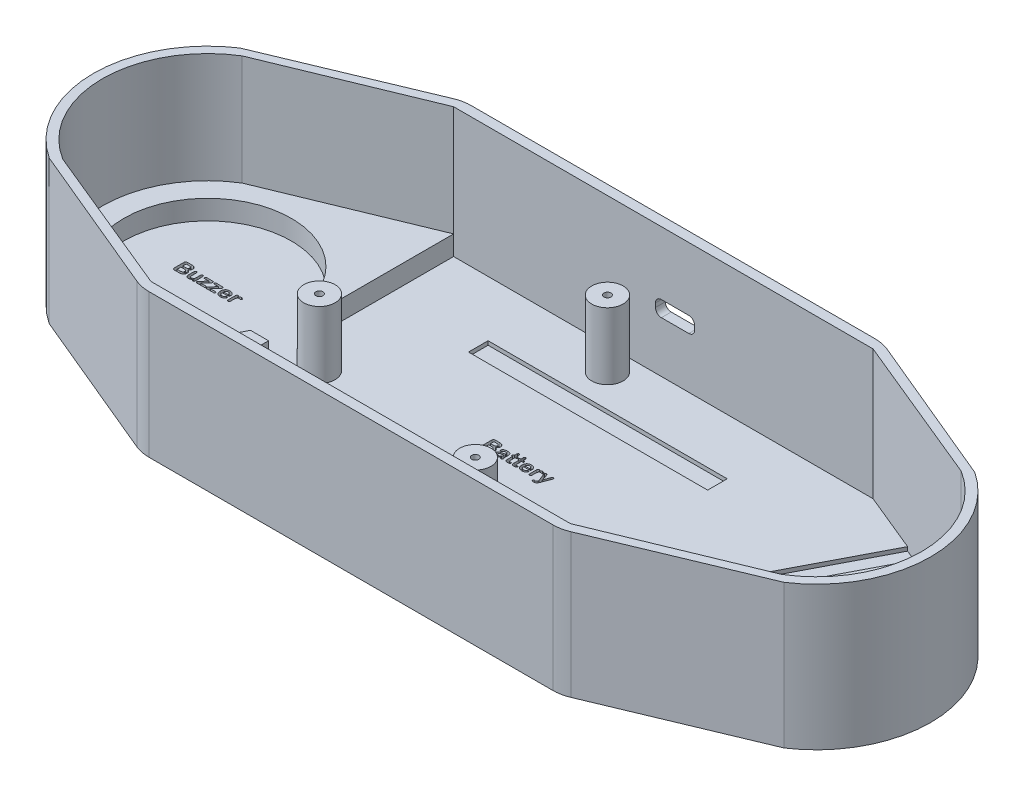
SolidWorks part; units mm, degrees
ref_plane "Front Plane" through (0, 0, 0) normal (0, 0, 1) x (1, 0, 0)
ref_plane "Top Plane" through (0, 0, 0) normal (0, 1, 0) x (1, 0, 0)
ref_plane "Right Plane" through (0, 0, 0) normal (1, 0, 0) x (0, 0, -1)
sketch "Sketch2" plane through (0, 0, 0) normal (0, 1, 0) x (1, 0, 0)
  line L0 (0, 0) -> (102, 0) construction
  line L1 (0, 0) -> (0, -77.2) construction
  line L2 (102, 0) -> (102, -77.2) construction
  line L3 (0, -77.2) -> (102, -77.2) construction
  line L4 (51, 0) -> (51, -77.2) construction
  line L5 (0, -38.6) -> (102, -38.6) construction
  line L6 (-2.5, 2.5) -> (104.5, 2.5)
  line L7 (-2.5, -79.7) -> (104.5, -79.7)
  line L8 (104.5, 2.5) -> (144.7372, -14.2911)
  line L9 (104.5, -79.7) -> (144.7372, -62.9089)
  line L10 (102, -38.6) -> (155.3, -38.6) construction
  line L11 (-2.5, -79.7) -> (-42.7372, -62.9089)
  line L12 (-2.5, 2.5) -> (-42.7372, -14.2911)
  line L13 (0, 0) -> (102, 0)
  line L14 (102, 0) -> (104.5, 0)
  line L15 (104.5, 0) -> (142.7026, -15.7437)
  line L16 (104.5, -77.2) -> (142.7026, -61.4563)
  line L17 (102, -77.2) -> (104.5, -77.2)
  line L18 (-2.5, -77.2) -> (-40.7026, -61.4563)
  line L19 (0, -77.2) -> (-2.5, -77.2)
  line L20 (-2.5, 0) -> (-40.7026, -15.7437)
  line L21 (0, 0) -> (-2.5, 0)
  line L22 (0, -77.2) -> (102, -77.2)
  line L23 (0, -76.7) -> (102, -76.7) construction
  line L24 (-2.5, -38.6) -> (-53.4807, -38.6) construction
  line L25 (-2.5, 0) -> (-2.5, -77.2) construction
  line L26 (104.5, 0) -> (104.5, -77.2) construction
  line L27 (0.5, 0) -> (0.5, -77.2) construction
  arc A0 (144.7372, -14.2911) -> (144.7372, -62.9089) centre (128.65, -38.6) cw
  arc A1 (-42.7372, -14.2911) -> (-42.7372, -62.9089) centre (-26.65, -38.6) ccw
  arc A2 (142.7026, -15.7437) -> (142.7026, -61.4563) centre (128.65, -38.6) cw
  arc A3 (-40.7026, -15.7437) -> (-40.7026, -61.4563) centre (-26.65, -38.6) ccw
  circle A4 centre (5.55, -71.7) radius 1.1
  circle A5 centre (5.6, -42.325) radius 1.1
  circle A6 centre (61.615, -58.575) radius 1.1
  circle A7 centre (42.614, -5.87) radius 1.1
  point P16 (157.8, -38.6)
  dimension "D3" = 2.5
  dimension "D10" = 2.5
  dimension "D11" = 5.05
  dimension "D12" = 5
  dimension "D13" = 34.375
  dimension "D15" = 18.125
  dimension "D17" = 42.114
  dimension "D1" = 77.2
  dimension "D2" = 102
  dimension "D4" = 2.5
  dimension "D5" = 2.5
  dimension "D6" = 2.5
  dimension "D7" = 0.5
  dimension "D8" = 2.5
  dimension "D9" = 53.3
  dimension "D14" = 5.1
  dimension "D16" = 61.115
  dimension "D18" = 70.83
  dimension "D19" = 0.5
extrude "MainExtrude" add sketch "Sketch2" along normal blind 33.1 contours A1 L11 L7 L9 A0 L8 L6 L12
extrude "MainCut" cut sketch "Sketch2<5>" along normal blind 50.8 contours L20 A3 L18 L19 L22 L17 L16 A2 L15 L14 L13 L21
sketch "Sketch2<5>" plane through (0, 0, 0) normal (0, 1, 0) x (1, 0, 0) same geometry as "Sketch2"
extrude "BassExtrude" add sketch "Sketch2<6>" against normal blind 3.5 contours L12 A1 L11 L7 L9 A0 L8 L6
sketch "Sketch2<6>" plane through (0, 0, 0) normal (0, 1, 0) x (1, 0, 0) same geometry as "Sketch2"
fillet "Fillet1" radius 10 4 edges at (104.5, 14.8, -2.5) (-2.5, 14.8, -2.5) (104.5, 14.8, 79.7) (-2.5, 14.8, 79.7)
sketch "Sketch6" plane through (0, 0, 0) normal (0, 1, 0) x (1, 0, 0)
  line L1 (-2.5, 0) -> (-2.5, -30)
  line L2 (-2.5, 0) -> (-2.5, -77.2) construction
  line L4 (-2.5, -77.2) -> (-2.5, -47.2)
  line L5 (-2.5, -47.2) -> (-52.065, -47.2) construction
  line L6 (-2.5, -30) -> (-52.065, -30) construction
  line L7 (-7.1001, -30) -> (-2.5, -30)
  line L8 (-2.5, -47.2) -> (-7.1001, -47.2)
  line L9 (-2.5, 0) -> (-40.7026, -15.7437)
  line L10 (-2.5, -77.2) -> (-40.7026, -61.4563)
  arc A2 (-40.7026, -15.7437) -> (-40.7026, -61.4563) centre (-26.65, -38.6) ccw
  arc A3 (-7.1001, -30) -> (-7.1001, -47.2) centre (-26.65, -38.6) ccw
  dimension "D1" = 30
  dimension "D2" = 30
extrude "Buzzer" add sketch "Sketch6" along normal blind 5
sketch "Sketch8" plane through (0, 0, 0) normal (0, 1, 0) x (1, 0, 0)
  text T0 "Buzzer" font "Arial Rounded MT Bold" height 3.5
  text T1 "Battery" font "Arial Rounded MT Bold" height 3.5
  text T2 "Speaker" font "Arial Rounded MT Bold" height 3.5
extrude "Text" cut sketch "Sketch8" against normal blind 1
sketch "Sketch9" plane through (0, 0, 0) normal (0, 1, 0) x (1, 0, 0)
  line L1 (104.5, -77.2) -> (104.5, -42.2)
  line L2 (104.5, 0) -> (104.5, -77.2) construction
  line L5 (104.5, -35) -> (109.5, -35)
  line L15 (104.5, -42.2) -> (109.5, -42.2)
  line L16 (109.5, -42.2) -> (109.5, -75.1394)
  line L17 (104.5, -77.2) -> (142.7026, -61.4563) construction
  line L18 (109.5, -75.1394) -> (104.5, -77.2)
  line L19 (109.5, -35) -> (123.6013, -7.8719)
  line L20 (104.5, 0) -> (142.7026, -15.7437) construction
  line L21 (104.5, -35) -> (119.4834, -6.1748)
  line L22 (142.7026, -15.7437) -> (104.5, 0) construction
  line L23 (119.4834, -6.1748) -> (123.6013, -7.8719)
  dimension "D3" = 5
  dimension "D2" = 35
  dimension "D4" = 5
sketch "Sketch10" plane through (0, 0, 0) normal (0, 1, 0) x (1, 0, 0)
  line L1 (20.5, -19.2) -> (81.5, -19.2)
  line L3 (20.5, -57.2) -> (51, -57.2)
  line L6 (20.5, -19.2) -> (20.5, -14.2)
  line L11 (20.5, -14.2) -> (81.5, -14.2)
  line L12 (81.5, -14.2) -> (81.5, -19.2)
  line L13 (20.5, -57.2) -> (20.5, -62.2)
  line L14 (20.5, -62.2) -> (51, -62.2)
  line L15 (51, -62.2) -> (51, -57.2)
  line L16 (51, 0) -> (51, -77.2) construction
  dimension "D1" = 0
  dimension "D2" = 5
  dimension "D3" = 38
  dimension "D4" = 61
  dimension "D5" = 5
  dimension "D6" = 30.5
extrude "Battery Cover Molds" cut sketch "Sketch10" against normal blind 1
sketch "Sketch11" plane through (0, 0, 0) normal (0, 1, 0) x (1, 0, 0)
  circle A0 centre (5.6, -42.325) radius 0.9
  circle A1 centre (5.6, -42.325) radius 4
  circle A2 centre (5.55, -71.7) radius 0.9
  circle A3 centre (5.55, -71.7) radius 4
  circle A4 centre (61.615, -58.575) radius 0.9
  circle A5 centre (61.615, -58.575) radius 4
  circle A6 centre (42.614, -5.87) radius 0.9
  circle A7 centre (42.614, -5.87) radius 4
extrude "PCB Offsets" add sketch "Sketch11" along normal blind 17
sketch "Sketch12" plane through (0, 0, -2.5) normal (0, 0, -1) x (-1, 0, 0)
  line L0 (-51, 0) -> (-51, 33.1) construction
  line L1 (2.5, 0) -> (-104.5, 0) construction
  line L2 (0.4972, 33.1) -> (-102.4972, 33.1) construction
  line L3 (-102.4972, 17) -> (0.4972, 17) construction
  line L4 (-102.4972, 33.1) -> (-102.4972, -3.5) construction
  line L5 (0.4972, -3.5) -> (0.4972, 33.1) construction
  line L8 (2.5, 0) -> (-104.5, 0) construction
  line L10 (-59, 17) -> (-49, 17)
  line L11 (-59, 17) -> (-59, 13)
  line L12 (-59, 13) -> (-49, 13)
  line L13 (-49, 17) -> (-49, 13)
  dimension "D1" = 17
  dimension "D2" = 4
  dimension "D3" = 10
  dimension "D4" = 2
extrude "USB" cut sketch "Sketch12" against normal up to next
fillet "Fillet2" radius 1.5 4 edges at (49, 13, -1.25) (59, 13, -1.25) (49, 17, -1.25) (59, 17, -1.25)
extrude "Cut-Extrude1" cut sketch "Sketch9" against normal blind 1
sketch "Sketch13" plane through (0, 5, 0) normal (0, 1, 0) x (1, 0, 0)
  line L0 (-51.1151, -27.5844) -> (-44.948, -27.5844)
  line L1 (-51.1151, -49.6156) -> (-44.948, -49.6156)
  line L2 (-48.0079, -38.6) -> (-53.4807, -38.6) construction
  line L3 (-50.7443, -43.2627) -> (-50.7443, -32.5646) construction
  arc A0 (-51.1151, -49.6156) -> (-51.1151, -27.5844) centre (-26.65, -38.6) cw
  arc A1 (-40.7026, -15.7437) -> (-40.7026, -61.4563) centre (-26.65, -38.6) ccw construction
  arc A2 (-40.7026, -15.7437) -> (-40.7026, -61.4563) centre (-26.65, -38.6) ccw construction
  arc A3 (-7.1001, -30) -> (-7.1001, -47.2) centre (-26.65, -38.6) ccw construction
  arc A4 (-44.948, -27.5844) -> (-44.948, -49.6156) centre (-26.65, -38.6) ccw
  circle A5 centre (-50.7443, -38.6) radius 1.7
